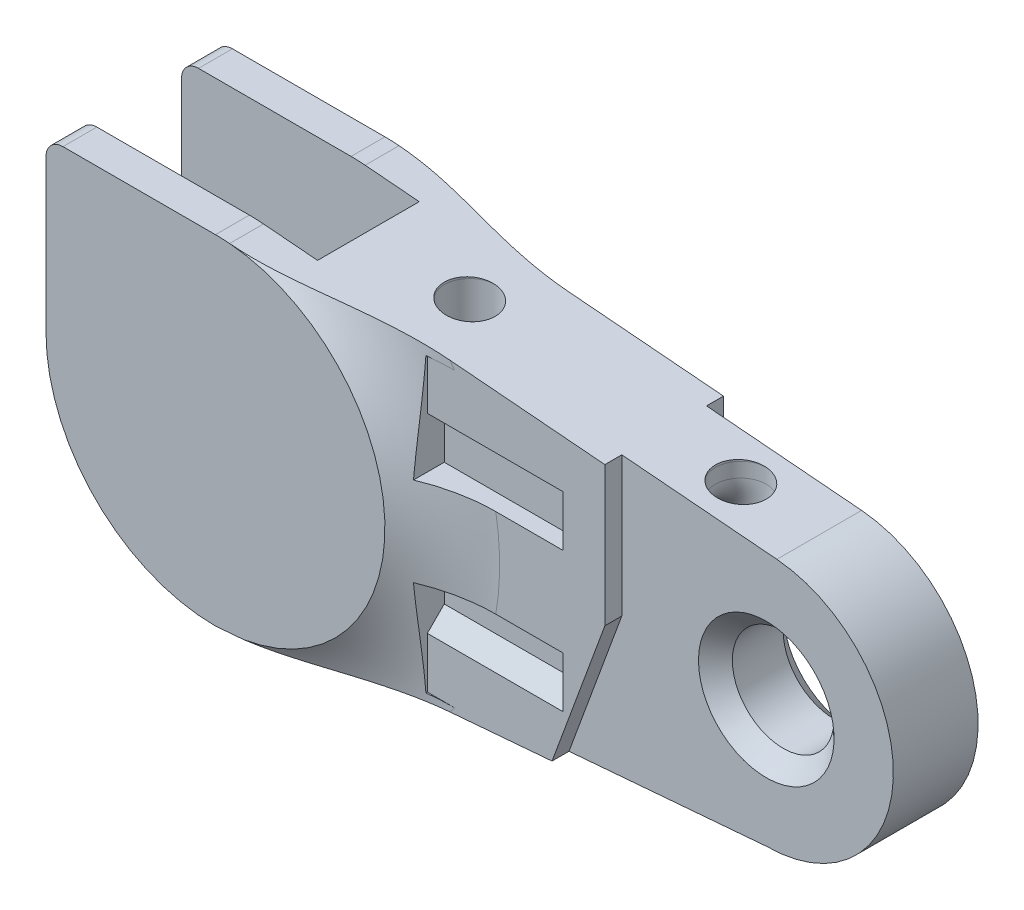
SolidWorks part; units mm, degrees
ref_plane "Front Plane" through (0, 0, 0) normal (0, 0, 1) x (1, 0, 0)
ref_plane "Top Plane" through (0, 0, 0) normal (0, 1, 0) x (1, 0, 0)
ref_plane "Right Plane" through (0, 0, 0) normal (1, 0, 0) x (0, 0, -1)
sketch "Sketch1" plane through (0, 0, 0) normal (0, 0, 1) x (1, 0, 0)
  line L0 (55, 0) -> (-55, 0) construction
  line L1 (0, -55) -> (0, 55) construction
  line L2 (-14.1667, 9.9652) -> (15.625, 7.4739)
  line L3 (-15, -10) -> (15, -7.5)
  line L4 (-15, 10) -> (-24, 10)
  line L5 (-25, 9) -> (-25, 0)
  arc A0 (-25, 0) -> (-15, 10) centre (-15, 0) ccw
  circle A1 centre (15, 0) radius 7.5
  circle A2 centre (-15, 0) radius 2.5
  circle A3 centre (15, 0) radius 3
  arc A4 (-24, 10) -> (-25, 9) centre (-24, 9) ccw
  dimension "D1" = 20
  dimension "D2" = 15
  dimension "D5" = 5
  dimension "D6" = 6
  dimension "D7" = 1
  dimension "D3" = 30
  dimension "D4" = 15
extrude "Boss-Extrude1" add sketch "Sketch1" along normal mid plane 7 contours A1 L2 A0 L3 region at (0.9606, 0.0273, 0)
extrude "Boss-Extrude2" add sketch "Sketch1<3>" along normal mid plane 10 contours A0 L3 A2 region at (-5.2912, 0.4024, 0)
sketch "Sketch1<3>" plane through (0, 0, 0) normal (0, 0, 1) x (1, 0, 0) same geometry as "Sketch1"
extrude "Boss-Extrude3" add sketch "Sketch1<5>" along normal mid plane 9 contours A1 A3 region at (20.3637, 4.9339, 0)
sketch "Sketch1<5>" plane through (0, 0, 0) normal (0, 0, 1) x (1, 0, 0) same geometry as "Sketch1"
fillet "Fillet1" radius 10 2 edges at (-5.0086, 0.4141, -3.5) (-5.0086, 0.4141, 3.5)
extrude "Cut-Extrude2" cut sketch "Sketch1<6>" against normal mid plane 6 contours A0 L3 A2 region at (-5.2912, 0.4024, 0)
sketch "Sketch1<6>" plane through (0, 0, 0) normal (0, 0, 1) x (1, 0, 0) same geometry as "Sketch1"
sketch "Sketch2" plane through (0, 0, 0) normal (0, 0, 1) x (1, 0, 0)
  line L0 (-4.5, 0) -> (-4.5, -10.5)
  line L1 (-4.5, -10.5) -> (-15, -10.5)
  line L2 (6.4759, 0) -> (3, -9.4488)
  line L3 (3, -9.4488) -> (15, -9.4488)
  line L4 (15, -9.4488) -> (15, -8)
  line L5 (6.4759, 0) -> (16.0501, 0)
  line L6 (55, 0) -> (-55, 0) construction
  line L7 (6.4759, 0) -> (6.4759, 8.8777)
  line L8 (6.4759, 8.8777) -> (15, 8)
  arc A0 (-4.5, 0) -> (-15, -10.5) centre (-15, 0) ccw
  arc A1 (15, -8) -> (15, 8) centre (15, 0) ccw
  dimension "D1" = 21
  dimension "D2" = 16
  dimension "D3" = 12
extrude "Cut-Extrude3" cut sketch "Sketch2" against normal mid plane 6 contours L0 A0 L1 region at (-14.4786, -0.5214, 0)
extrude "Cut-Extrude4" cut sketch "Sketch2<3>" along normal blind 7.5 from offset 10 contours A1 region at (13.245, -0.6687, 0) offset against normal yes
sketch "Sketch2<3>" plane through (0, 0, 0) normal (0, 0, 1) x (1, 0, 0) same geometry as "Sketch2"
mirror "Mirror1" about plane through (0, 0, 0) normal (0, 0, 1) of "Cut-Extrude4"
sketch "Sketch3" plane through (0, 0, 0) normal (0, 0, 1) x (1, 0, 0)
  line L0 (-5, 9.1987) -> (-5, 7)
  line L1 (-2.6696, 9.0038) -> (-14.1667, 9.9652) construction
  line L2 (-2, 4) -> (8, 4)
  line L3 (11, 7) -> (11, 7.8607)
  line L4 (-2.6696, 9.0038) -> (6.4759, 8.239) construction
  line L5 (-5, 9.1987) -> (-5, 11.3767)
  line L7 (11, 7.8607) -> (11, 10.9782)
  line L8 (0, -55) -> (0, 55) construction
  line L9 (55, 0) -> (-55, 0) construction
  arc A2 (11, 7) -> (8, 4) centre (8, 7) cw
  arc A3 (-2, 4) -> (-5, 7) centre (-2, 7) cw
  point P24 (11, 4)
  point P27 (-5, 4)
  dimension "D1" = 16
  dimension "D2" = 5
  dimension "D3" = 4
sweep "Cut-Sweep5" cut path "Sketch3" circular profile diameter 3 parameters "D3"=3
mirror "Mirror2" about plane through (0, 0, 0) normal (0, 1, 0) of "Cut-Sweep5"
extrude "Boss-Extrude4" add sketch "Sketch1<7>" along normal mid plane 10 contours A2 region at (-15, 0, 0)
sketch "Sketch1<7>" plane through (0, 0, 0) normal (0, 0, 1) x (1, 0, 0) same geometry as "Sketch1"
chamfer "Chamfer1" distance 1 angle 45 4 edges at (18, 0, -2.5) (12, 0, 2.5) (-12.5, 0, 3) (-12.5, 0, -3)
sketch "Sketch139" plane through (0, 0, 0) normal (1, 0, 0) x (0, 0, -1)
  line L0 (3.5, 8.6214) -> (3.5, 5.6214)
  line L1 (3.5, 9.0038) -> (3.5, 8.239) construction
  line L2 (3.5, 8.239) -> (3.5, 0) construction
  line L3 (3.5, 5.6214) -> (2.5, 4.6214)
  line L4 (2.5, 4.6214) -> (2.5, 2.6214)
  line L5 (2.5, 2.6214) -> (5.5203, 2.6214)
  line L6 (5.5203, 2.6214) -> (5.5203, 8.6214)
  line L7 (5.5203, 8.6214) -> (3.5, 8.6214)
  dimension "D1" = 3
  dimension "D2" = 1
  dimension "D3" = 1
  dimension "D4" = 2
extrude "Cut-Extrude5" cut sketch "Sketch139" against normal mid plane 8
mirror "Mirror3" about plane through (0, 0, 0) normal (0, 1, 0) of "Cut-Extrude5"
mirror "Mirror4" about plane through (0, 0, 0) normal (0, 0, 1) of "Mirror3"
